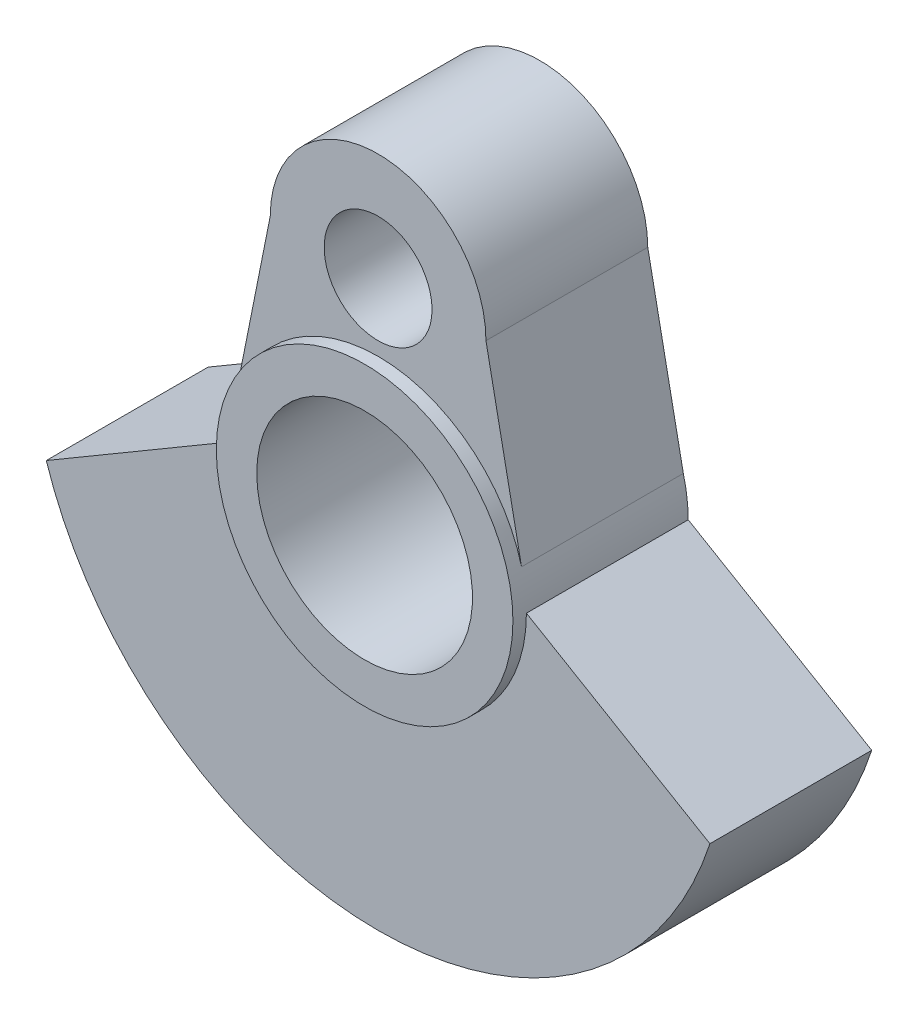
SolidWorks part; units mm, degrees
ref_plane "Front Plane" through (0, 0, 0) normal (0, 0, 1) x (1, 0, 0)
ref_plane "Top Plane" through (0, 0, 0) normal (0, 1, 0) x (1, 0, 0)
ref_plane "Right Plane" through (0, 0, 0) normal (1, 0, 0) x (0, 0, -1)
sketch "Sketch1" plane through (0, 0, 0) normal (0, 0, 1) x (1, 0, 0)
  line L0 (0, 0) -> (0, 8) construction
  line L1 (0, 8) -> (0, 0) construction
  line L2 (0, 0) -> (-13.9521, 0) construction
  line L3 (-12.3051, -4) -> (-5.5, 0)
  line L4 (12.3051, -4) -> (5.5, 0)
  line L5 (-4, 8) -> (-5.3193, 1.3984)
  line L6 (4, 8) -> (5.3193, 1.3984)
  circle A0 centre (0, 0) radius 5.5
  arc A1 (4, 8) -> (-4, 8) centre (0, 8) ccw
  circle A2 centre (0, 8) radius 2
  arc A3 (-12.3051, -4) -> (12.3051, -4) centre (0, 0) ccw
  circle A4 centre (0, 0) radius 4
  dimension "D1" = 11
  dimension "D2" = 8
  dimension "D3" = 4
  dimension "D4" = 12.9389
  dimension "D7" = 8
  dimension "D5" = 4
  dimension "D6" = 8
extrude "Boss-Extrude1" add sketch "Sketch1" along normal mid plane 6 contours L3 A3 L4 A0 | L6 A1 L5 A0 A2 region at (0, -6.9887, 0) region at (-4.5124, 4.6698, 0)
extrude "Boss-Extrude2" add sketch "Sketch1<3>" along normal blind 6.5 from surface contours A0 A4 region at (-5.3003, 0.6851, 0) starting at face at (0, -5.6097, -3)
sketch "Sketch1<3>" plane through (0, 0, 0) normal (0, 0, 1) x (1, 0, 0) same geometry as "Sketch1"
